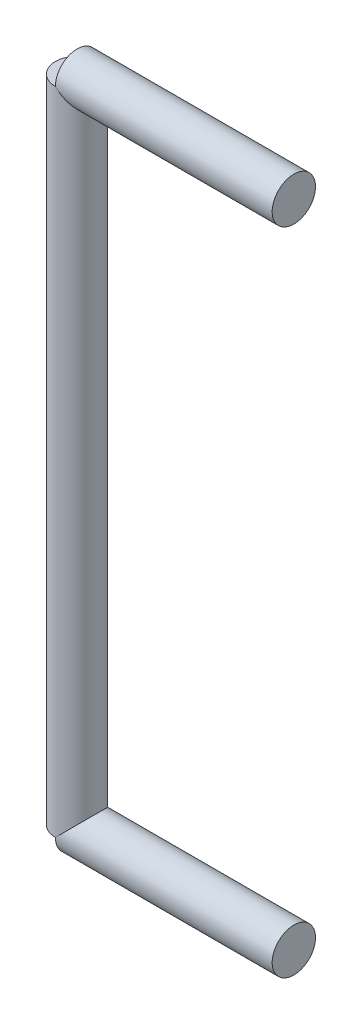
SolidWorks part; units mm, degrees
ref_plane "Front Plane" through (0, 0, 0) normal (0, 0, 1) x (1, 0, 0)
ref_plane "Top Plane" through (0, 0, 0) normal (0, 1, 0) x (1, 0, 0)
ref_plane "Right Plane" through (0, 0, 0) normal (1, 0, 0) x (0, 0, -1)
sketch "Sketch1" plane through (0, 0, 0) normal (0, 1, 0) x (1, 0, 0)
  circle A0 centre (0, 0) radius 0.5
  dimension "D1" = 1
extrude "Boss-Extrude2" add sketch "Sketch1" along normal blind 15
sketch "Sketch9" plane through (0, 0, 0) normal (1, 0, 0) x (0, 0, -1)
  line L0 (0.5, 15) -> (-0.5, 15) construction
  line L1 (-0.5, 0) -> (0.5, 0) construction
  circle A0 centre (0, 0) radius 0.5
  circle A1 centre (0, 15) radius 0.5
  dimension "D1" = 1
  dimension "D2" = 1
extrude "Boss-Extrude3" add sketch "Sketch9" along normal blind 5
